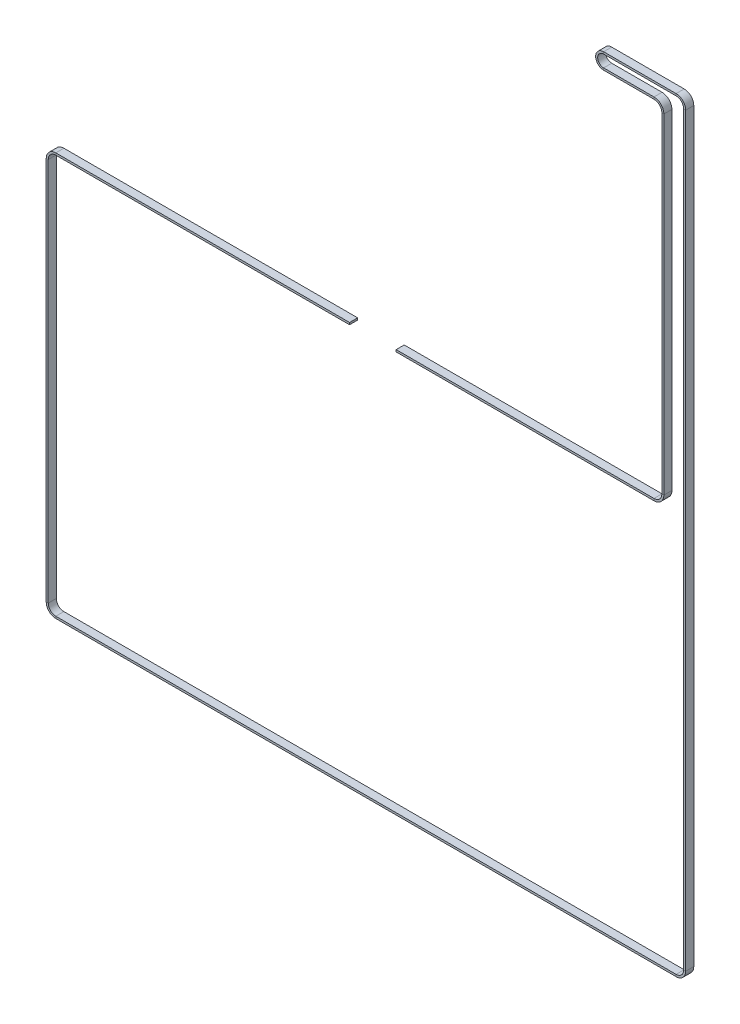
SolidWorks part; units mm, degrees
ref_plane "Front" through (0, 0, 0) normal (0, 0, 1) x (1, 0, 0)
ref_plane "Top" through (0, 0, 0) normal (0, 1, 0) x (1, 0, 0)
ref_plane "Right" through (0, 0, 0) normal (1, 0, 0) x (0, 0, -1)
sketch "Sketch1" plane through (0, 0, 2.2) normal (0, 0, 1) x (1, 0, 0)
  line L0 (377.3122, -142.2854) -> (431.3122, -142.2854)
  line L1 (377.3122, -152.6854) -> (414.8122, -152.6854)
  line L2 (421.4122, -159.2854) -> (421.4122, -405.0573)
  line L3 (437.6872, -148.6604) -> (437.6872, -703.9854)
  line L4 (-37.0628, -703.9854) -> (-37.0628, -417.8823)
  line L5 (431.3122, -710.3604) -> (-30.6878, -710.3604)
  line L6 (-30.6878, -411.5073) -> (188.0908, -411.5073)
  line L7 (222.7908, -410.0573) -> (222.7908, -415.0573) construction
  line L9 (414.8122, -411.6573) -> (222.7908, -411.6573)
  line L10 (188.0908, -415.0573) -> (188.0908, -410.0573) construction
  circle A0 centre (414.8122, -159.2854) radius 6.6 construction
  circle A1 centre (431.3122, -148.6604) radius 6.375 construction
  circle A2 centre (377.3122, -147.4854) radius 5.2 construction
  arc A3 (431.3122, -142.2854) -> (437.6872, -148.6604) centre (431.3122, -148.6604) cw
  arc A4 (377.3122, -152.6854) -> (377.3122, -142.2854) centre (377.3122, -147.4854) cw
  arc A5 (414.8122, -152.6854) -> (421.4122, -159.2854) centre (414.8122, -159.2854) cw
  circle A6 centre (-30.6878, -703.9854) radius 6.375 construction
  arc A7 (-30.6878, -710.3604) -> (-37.0628, -703.9854) centre (-30.6878, -703.9854) cw
  circle A8 centre (431.3122, -148.6604) radius 9 construction
  circle A9 centre (414.8122, -159.2854) radius 9 construction
  circle A11 centre (431.3122, -703.9854) radius 6.375 construction
  arc A12 (437.6872, -703.9854) -> (431.3122, -710.3604) centre (431.3122, -703.9854) cw
  arc A13 (-37.0628, -417.8823) -> (-30.6878, -411.5073) centre (-30.6878, -417.8823) cw
  arc A15 (421.4122, -405.0573) -> (414.8122, -411.6573) centre (414.8122, -405.0573) cw
  circle A16 centre (-30.6878, -417.8823) radius 6.375 construction
  circle A17 centre (-30.6878, -417.8823) radius 5.9875 construction
  circle A18 centre (414.8122, -405.0573) radius 6.6 construction
  circle A19 centre (414.8122, -405.0573) radius 5.9875 construction
  dimension "D1" = 12.75
ref_plane "Plane1" through (188.0908, -411.5073, 2.2) normal (1, 0, 0) x (0, 0, -1)
sketch "Sketch4" plane through (188.0908, -411.5073, 2.2) normal (1, 0, 0) x (0, 0, -1)
  line L0 (0, 262.8469) -> (0, -292.4781) construction
  line L1 (3, -0.75) -> (-3, -0.75)
  line L2 (3, -0.75) -> (3, 0.75)
  line L3 (3, 0.75) -> (-3, 0.75)
  line L4 (-3, -0.75) -> (-3, 0.75)
  line L5 (3, -0.75) -> (-3, 0.75) construction
  line L6 (3, 0.75) -> (-3, -0.75) construction
  point P0 (0, 0)
  dimension "D1" = 1.5
  dimension "D2" = 6
sweep "Sweep1" add profiles "Sketch4" path "Sketch1"
